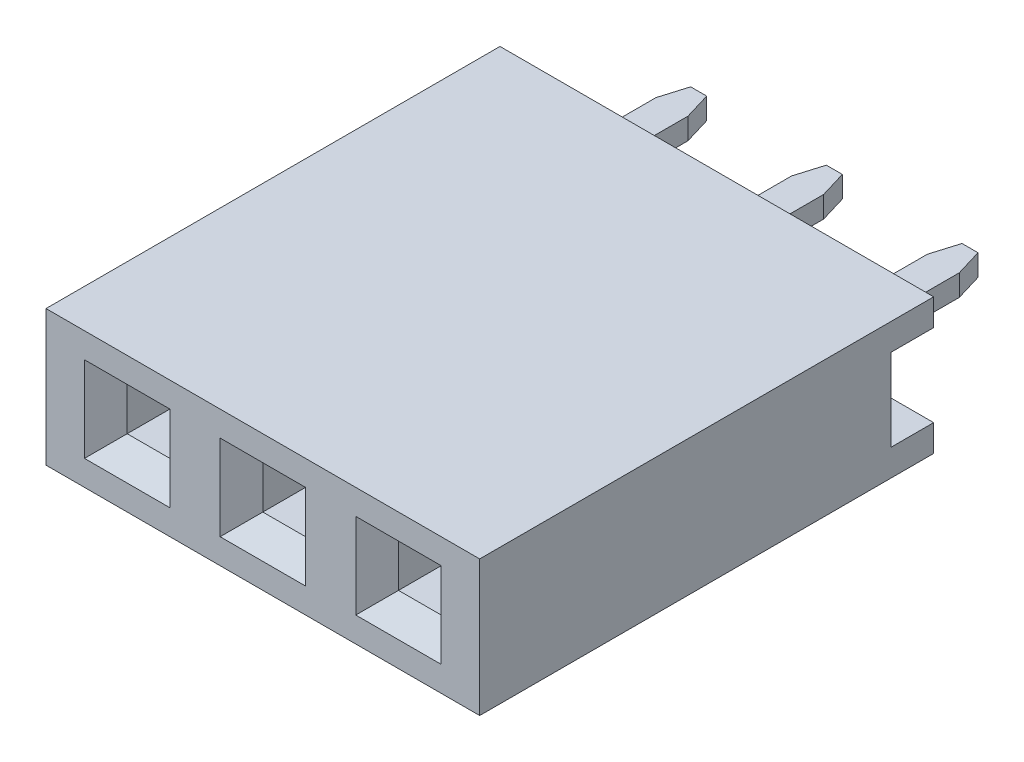
SolidWorks part; units mm, degrees
ref_plane "Front Plane" through (0, 0, 0) normal (0, 0, 1) x (1, 0, 0)
ref_plane "Top Plane" through (0, 0, 0) normal (0, 1, 0) x (1, 0, 0)
ref_plane "Right Plane" through (0, 0, 0) normal (1, 0, 0) x (0, 0, -1)
sketch "Sketch1" plane through (0, 0, 0) normal (1, 0, 0) x (0, -1, 0)
  line L0 (0, 0) -> (0, -8.5) construction
  line L1 (-1.27, 0) -> (1.27, 0)
  line L2 (-1.27, 0) -> (-1.27, -8.5)
  line L3 (-1.27, -8.5) -> (1.27, -8.5)
  line L4 (1.27, 0) -> (1.27, -8.5)
  point P0 (-1.27, -0.5022)
  dimension "D1" = 1.27
  dimension "D2" = 8.5
  dimension "D3" = 1.27
extrude "Boss-Extrude1" add sketch "Sketch1" along normal mid plane 3.04
sketch "Эскиз1" plane through (1.52, 0, 0) normal (1, 0, 0) x (0, 0, -1)
  line L0 (0, -0.77) -> (-0.8, -0.77)
  line L1 (0, -1.27) -> (0, 1.27) construction
  line L2 (-0.8, -0.77) -> (-0.8, 0.77)
  line L4 (-0.8, 0.77) -> (0, 0.77)
  line L5 (0, 0.77) -> (0, -0.77)
  line L6 (-8.5, -1.27) -> (0, -1.27) construction
  dimension "D1" = 0.5
  dimension "D2" = 0.8
  dimension "D3" = 0.5
extrude "Вырез-Вытянуть1" cut sketch "Эскиз1" against normal through all
sketch "Sketch2" plane through (0, 0, 8.5) normal (0, 0, 1) x (-1, 0, 0)
  line L0 (0, -1.27) -> (0, 1.27) construction
  line L3 (-1.52, -1.27) -> (1.52, -1.27) construction
  line L4 (-0.4, 0.4) -> (0.4, 0.4)
  line L5 (-0.4, 0.4) -> (-0.4, -0.4)
  line L6 (-0.4, -0.4) -> (0.4, -0.4)
  line L7 (0.4, 0.4) -> (0.4, -0.4)
  line L8 (-0.4, 0.4) -> (0.4, -0.4) construction
  line L9 (-0.4, -0.4) -> (0.4, 0.4) construction
  line L10 (-1.52, 1.27) -> (1.52, 1.27) construction
  point P5 (0, 0)
  dimension "D1" = 0.8
extrude "Cut-Extrude1" cut sketch "Sketch2" against normal blind 7
chamfer "Фаска1" distance 0.4 angle 45 4 edges at (0, -0.4, 8.5) (0.4, 0, 8.5) (0, 0.4, 8.5) (-0.4, 0, 8.5)
sketch "Sketch3" plane through (0, 0, 0) normal (0, 1, 0) x (1, 0, 0)
  line L0 (-0.3, 0) -> (-0.3, 1.7)
  line L1 (0.3, 0) -> (0.3, -0.8)
  line L2 (-0.3, 1.7) -> (-0.15, 2.2)
  line L3 (-0.15, 2.2) -> (0.15, 2.2)
  line L4 (0, 2.2) -> (0, 0) construction
  line L5 (-0.3, 0) -> (0.3, 0) construction
  line L6 (0.3, 1.7) -> (0.15, 2.2)
  line L7 (0.3, 0) -> (0.3, 1.7)
  line L8 (0.3, -0.8) -> (-0.3, -0.8)
  line L9 (-0.3, -0.8) -> (-0.3, 0)
  line L10 (-1.52, -0.8) -> (1.52, -0.8) construction
  line L11 (0.3, 1.7) -> (-0.3, 1.7) construction
  line L12 (0.4, -1.5) -> (-0.4, -1.5)
  line L13 (-0.4, -1.5) -> (-0.4, -6.9)
  line L14 (-0.4, -6.9) -> (-0.3, -6.9)
  line L15 (-0.3, -6.9) -> (-0.3, -1.6)
  line L16 (-0.3, -1.6) -> (0.3, -1.6)
  line L17 (0.3, -1.6) -> (0.3, -6.9)
  line L18 (0.3, -6.9) -> (0.4, -6.9)
  line L19 (0.4, -6.9) -> (0.4, -1.5)
  line L20 (-0.4, -1.5) -> (-0.4, -8.1) construction
  line L21 (0.4, -1.5) -> (0.4, -8.1) construction
  line L22 (-0.4, -1.5) -> (0.4, -1.5) construction
  point P28 (0.3, -3.1217)
  dimension "D1" = 0.6
  dimension "D2" = 0.3
  dimension "D3" = 2.2
  dimension "D4" = 0.5
  dimension "D5" = 1.6
  dimension "D6" = 0.1
  dimension "D7" = 0.1
extrude "Boss-Extrude2" add sketch "Sketch3" along normal mid plane 0.4
pattern_linear "LPattern1" count 3 spacing 2.54 along (1, 0, 0) of bodies 103
combine bodies "Соединить1" operation type add bodies to combine 107 104 103
